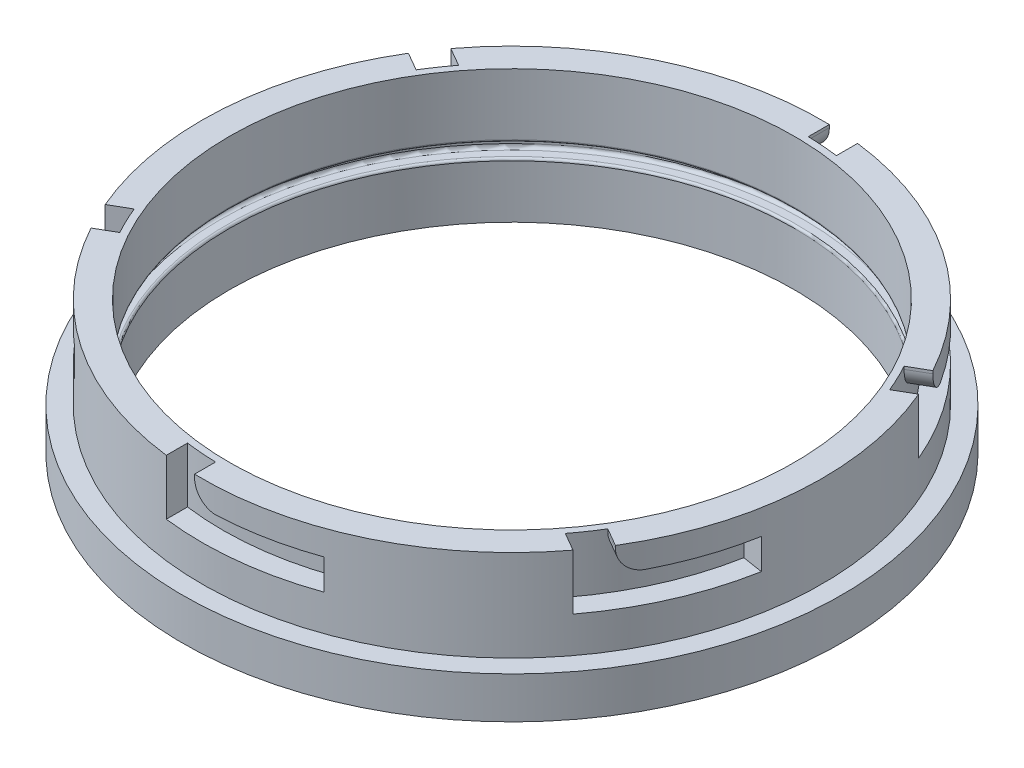
SolidWorks part; units mm, degrees
material "6061-T6 (SS)"
ref_plane "Front Plane" through (0, 0, 0) normal (0, 0, 1) x (1, 0, 0)
ref_plane "Top Plane" through (0, 0, 0) normal (0, 1, 0) x (1, 0, 0)
ref_plane "Right Plane" through (0, 0, 0) normal (1, 0, 0) x (0, 0, -1)
sketch "Sketch1" plane through (0, 0, 0) normal (0, 0, 1) x (1, 0, 0)
  line L0 (0, 60.758) -> (0, -61.3352) construction
  line L1 (71.12, 36.5125) -> (71.12, 15.5575)
  line L2 (71.12, 15.5575) -> (75.565, 15.5575)
  line L3 (75.565, 15.5575) -> (75.565, 6.0325)
  line L4 (75.565, 6.0325) -> (64.77, 6.0325)
  line L5 (64.77, 6.0325) -> (64.77, 18.7325)
  line L6 (64.77, 36.5125) -> (71.12, 36.5125)
  line L7 (64.77, 18.7325) -> (67.818, 18.7325)
  line L8 (67.818, 18.7325) -> (67.818, 21.9075)
  line L9 (67.818, 21.9075) -> (64.77, 21.9075)
  line L10 (64.77, 21.9075) -> (64.77, 36.5125)
  dimension "D1" = 6.35
  dimension "D2" = 9.525
  dimension "D3" = 30.48
  dimension "D4" = 71.12
  dimension "D5" = 75.565
  dimension "D6" = 3.048
  dimension "D7" = 12.7
  dimension "D8" = 15.875
revolve "Revolve1" add sketch "Sketch1" angle 360 about L0
sketch "Sketch2" plane through (0, 36.5125, 0) normal (0, 1, 0) x (1, 0, 0)
  line L0 (-8.6592, -70.5909) -> (-8.6592, -65.726)
  line L1 (-1.6742, -71.1003) -> (-1.6742, -66.2729)
  arc A0 (-1.6742, -71.1003) -> (-8.6592, -70.5909) centre (0, 0) cw
  circle A1 centre (0, 0) radius 71.12 construction
  arc A2 (-1.6742, -66.2729) -> (-8.6592, -65.726) centre (0, 0) cw
  dimension "D1" = 4.826
  dimension "D2" = 6.985
  dimension "D3" = 6.985
extrude "Cut-Extrude1" cut sketch "Sketch2" against normal blind 12.7
sketch "Sketch10" plane through (-1.6742, 0, 0) normal (-1, 0, 0) x (0, 0, 1)
  line L0 (66.2729, 23.8125) -> (66.2729, 30.7975)
  line L1 (66.2729, 23.8125) -> (66.2729, 36.5125) construction
  line L2 (66.2729, 30.7975) -> (71.1003, 30.7975)
  line L3 (71.1003, 23.8125) -> (71.1003, 36.5125) construction
  line L4 (71.1003, 30.7975) -> (71.1003, 23.8125)
  line L5 (71.1003, 23.8125) -> (66.2729, 23.8125)
  dimension "D1" = 6.985
ref_axis "Axis1" through (0, 6.0325, 0) along (0, 1, 0)
sketch "Sketch21" plane through (0, 23.8125, 0) normal (0, 1, 0) x (1, 0, 0)
  line L0 (-1.6742, -71.1003) -> (-1.6742, -66.2729) construction
  arc A0 (-1.6742, -73.5126) -> (73.4476, -3.5158) centre (0, 0) ccw
sketch "Sketch22" plane through (0, 23.8125, 0) normal (0, 1, 0) x (1, 0, 0)
  circle A1 centre (0, 0) radius 73.5317
sketch "Sketch23" plane through (0, 23.8125, 0) normal (0, 1, 0) x (1, 0, 0)
  arc A0 (-1.6742, -71.1003) -> (23.922, -66.9761) centre (0, 0) ccw
sweep "Cut-Sweep2" cut profiles "Sketch10" path "Sketch23"
fillet "Fillet1" radius 5.08 1 edges at (-1.6742, 30.7975, 68.6866)
pattern_circular "CirPattern1" count 6 over 360 about axis through (0, 60.758, 0) along (0, 1, 0) of "Fillet1", "Cut-Extrude1", "Cut-Sweep2" reverse direction yes
fillet "Fillet2" radius 0.762 2 edges at (-67.818, 21.9075, 0) (-67.818, 18.7325, 0)
fillet "Fillet3" radius 0.508 2 edges at (-64.77, 18.7325, 0) (-64.77, 21.9075, 0)
